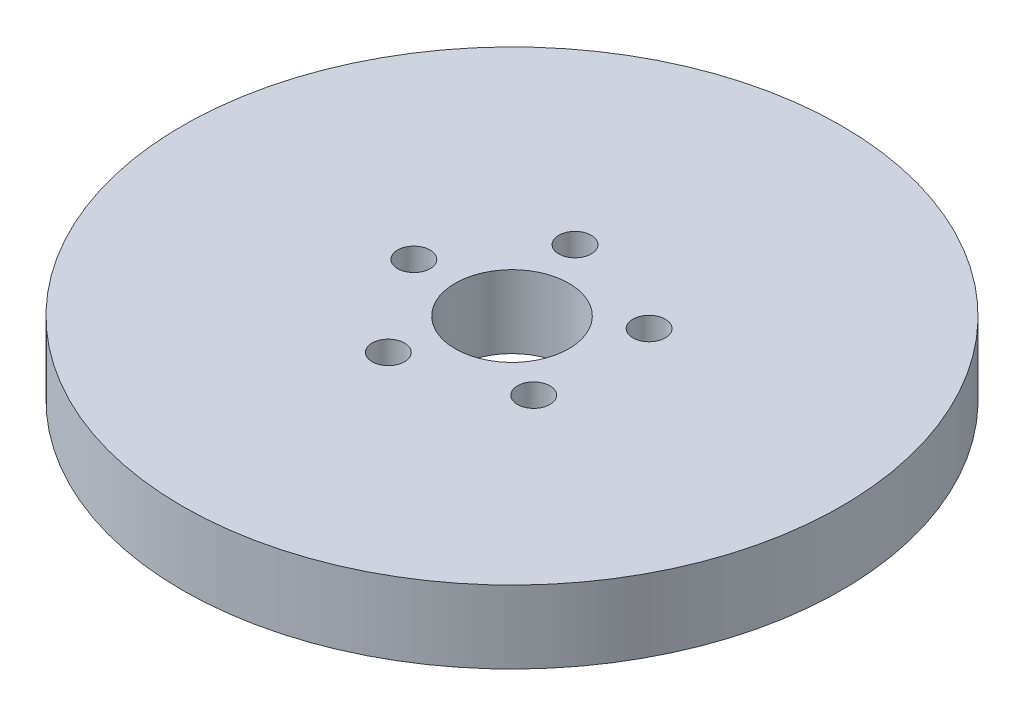
SolidWorks part; units mm, degrees
ref_plane "Front Plane" through (0, 0, 0) normal (0, 0, 1) x (1, 0, 0)
ref_plane "Top Plane" through (0, 0, 0) normal (0, 1, 0) x (1, 0, 0)
ref_plane "Right Plane" through (0, 0, 0) normal (1, 0, 0) x (0, 0, -1)
sketch "Sketch1" plane through (0, 0, 0) normal (0, 1, 0) x (1, 0, 0)
  circle A0 centre (0, 0) radius 72.5
  dimension "FLANGE_OD" = 145
extrude "Boss-Extrude1" add sketch "Sketch1" along normal blind 16
sketch "Sketch2" plane through (0, 0, 0) normal (0, 1, 0) x (1, 0, 0)
  circle A0 centre (0, 0) radius 12.5
  dimension "BORE_D" = 25
extrude "Cut-Extrude1" cut sketch "Sketch2" along normal through all
sketch "Sketch3" plane through (0, 16, 0) normal (0, 1, 0) x (1, 0, 0)
  circle A0 centre (0, 0) radius 21.5915 construction
  circle A1 centre (-21.5915, 0) radius 3.572
  dimension "BOLT_D" = 7.1441
  dimension "BOLT_PCD" = 43.183
extrude "Cut-Extrude2" cut sketch "Sketch3" against normal blind 13.9286
pattern_circular "CirPattern1" count 5 over 360 about axis through (0, 0, 0) along (0, 1, 0) of "Cut-Extrude2"
